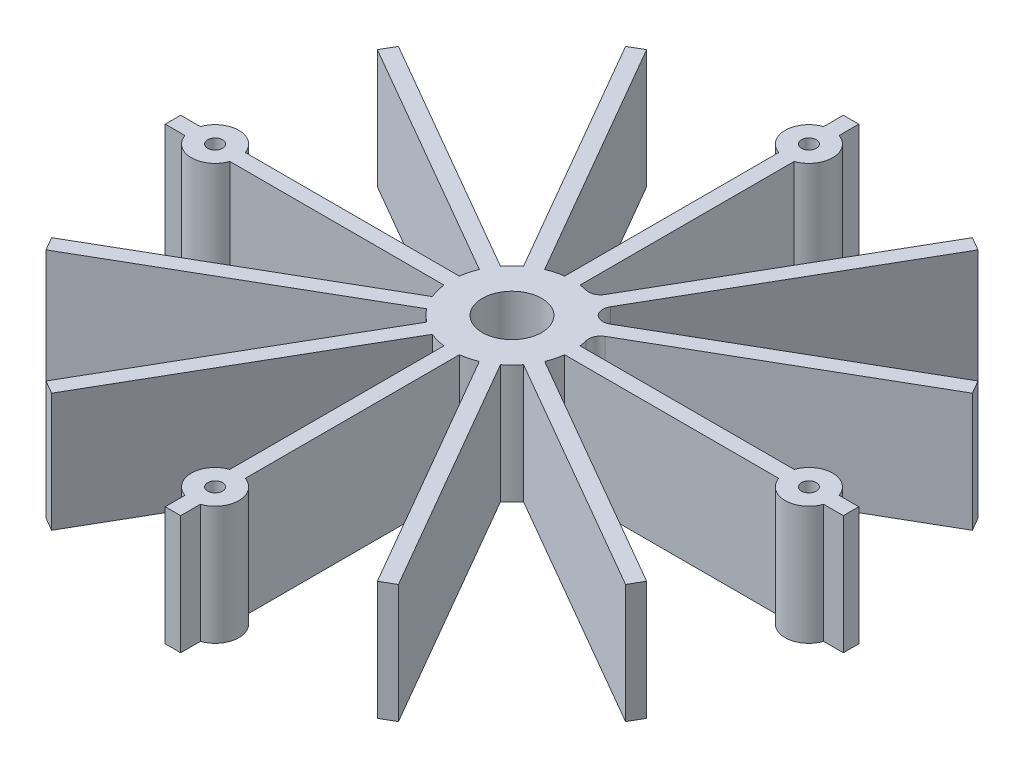
SolidWorks part; units mm, degrees
material "Magnesium Alloy"
ref_plane "Front Plane" through (0, 0, 0) normal (0, 0, 1) x (1, 0, 0)
ref_plane "Top Plane" through (0, 0, 0) normal (0, 1, 0) x (1, 0, 0)
ref_plane "Right Plane" through (0, 0, 0) normal (1, 0, 0) x (0, 0, -1)
sketch "Sketch1" plane through (0, 0, 0) normal (0, 0, 1) x (1, 0, 0)
  line L0 (55, 0) -> (-55, 0) construction
  line L1 (6.35, 12.7) -> (13.0175, 12.7)
  line L2 (6.35, 12.7) -> (6.35, -12.7)
  line L3 (6.35, -12.7) -> (13.0175, -12.7)
  line L4 (13.0175, 12.7) -> (13.0175, -12.7)
  line L5 (0, -55) -> (0, 55) construction
  line L6 (0, 37.2781) -> (0, -34.757) construction
  dimension "D1" = 6.6675
  dimension "D2" = 12.7
  dimension "D3" = 12.7
  dimension "D4" = 6.35
revolve "Revolve1" add sketch "Sketch1" angle 360 about L6
sketch "Sketch2" plane through (0, 12.7, 0) normal (0, 1, 0) x (1, 0, 0)
  line L0 (0, -55) -> (0, 55) construction
  line L5 (-55, 0) -> (55, 0) construction
  line L7 (-1.651, -10.16) -> (1.651, -10.16)
  line L8 (-1.651, -10.16) -> (-1.651, -72.517)
  line L9 (-1.651, -72.517) -> (1.651, -72.517)
  line L10 (1.651, -10.16) -> (1.651, -72.517)
  dimension "D5" = 62.357
  dimension "D6" = 3.302
  dimension "D7" = 1.651
  dimension "D8" = 10.16
extrude "Boss-Extrude1" add sketch "Sketch2" against normal blind 25.4
pattern_circular "CirPattern1" count 12 over 360 about axis through (0, 37.2781, 0) along (0, 1, 0) of "Boss-Extrude1"
sketch "Sketch3" plane through (0, 0, 0) normal (0, 1, 0) x (1, 0, 0)
  line L0 (0, -17.4216) -> (0, 17.4216) construction
  line L1 (-3.175, 3.175) -> (3.175, 3.175)
  line L2 (-3.175, 3.175) -> (-3.175, 9.525)
  line L3 (-3.175, 9.525) -> (3.175, 9.525)
  line L4 (3.175, 3.175) -> (3.175, 9.525)
  line L5 (-17.4216, 0) -> (17.4216, 0) construction
  dimension "D1" = 6.35
  dimension "D2" = 6.35
  dimension "D3" = 3.175
  dimension "D4" = 3.175
extrude "Cut-Extrude1" [suppressed] cut sketch "Sketch3" against normal mid plane 38.1
ref_axis "Axis1" through (0, -12.7, 0) along (0, 1, 0)
fillet "Fillet1" radius 2.54 4 edges at (12.0079, 0, -5.0264) (7.886, 0, -10.3569) (10.3569, 0, -7.886) (5.0264, 0, -12.0079)
sketch "Sketch4" plane through (0, 12.7, 0) normal (0, 1, 0) x (1, 0, 0)
  line L0 (0, -13.97) -> (0, 13.97) construction
  circle A0 centre (0, 63.5) radius 1.5875
  circle A1 centre (0, 63.5) radius 5.08
  dimension "D1" = 3.175
  dimension "D2" = 10.16
  dimension "D3" = 63.5
extrude "Boss-Extrude2" add sketch "Sketch4" against normal blind 25.4
sketch "Sketch5" plane through (0, 12.7, 0) normal (0, 1, 0) x (1, 0, 0)
  circle A0 centre (0, 63.5) radius 1.5875
  dimension "D1" = 3.175
  dimension "D2" = 63.5
extrude "Cut-Extrude2" cut sketch "Sketch5" against normal blind 25.4
pattern_circular "CirPattern2" count 4 over 360 about axis through (0, 37.2781, 0) along (0, 1, 0) of "Boss-Extrude2", "Cut-Extrude2" reverse direction yes
